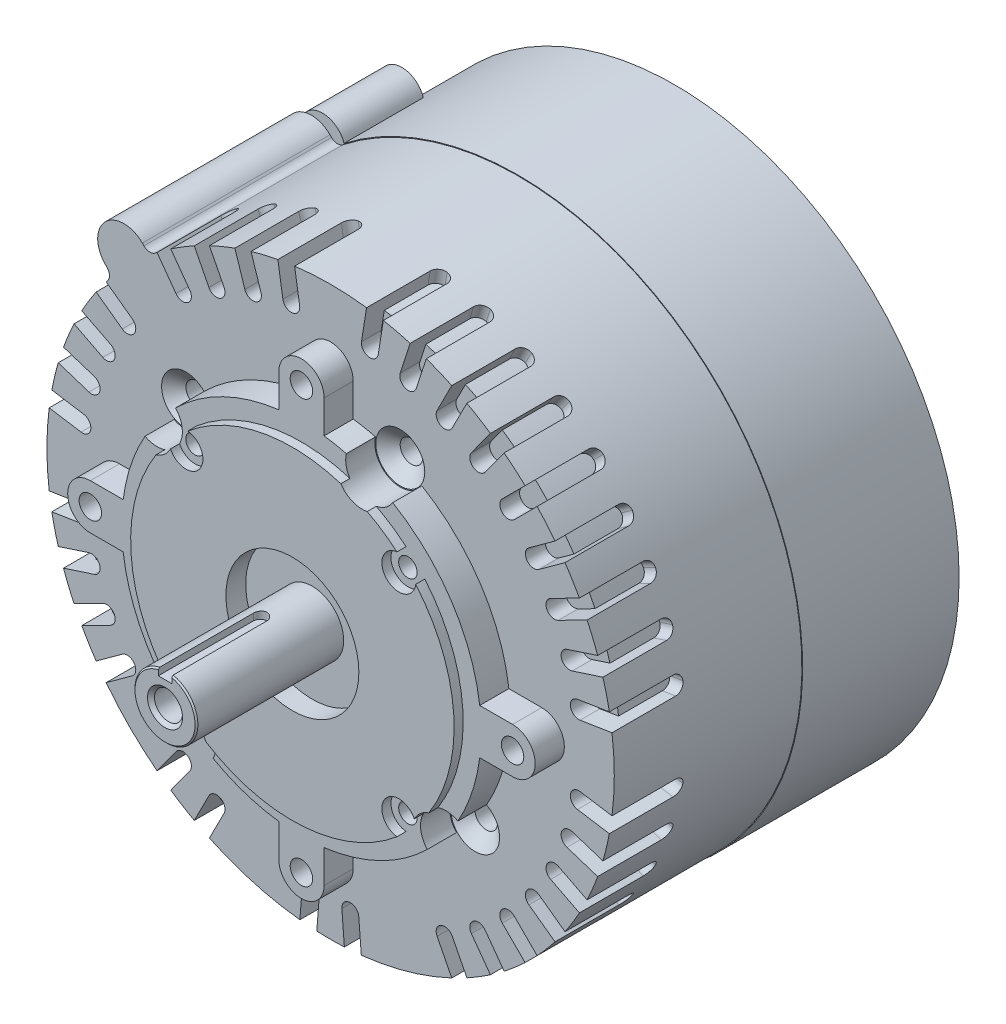
SolidWorks part; units mm, degrees
ref_plane "Front Plane" through (0, 0, 0) normal (0, 0, 1) x (1, 0, 0)
ref_plane "Top Plane" through (0, 0, 0) normal (0, 1, 0) x (1, 0, 0)
ref_plane "Right Plane" through (0, 0, 0) normal (1, 0, 0) x (0, 0, -1)
sketch "Sketch72" plane through (0, 0, 0) normal (0, 0, 1) x (1, 0, 0)
  circle A0 centre (0, 0) radius 100.5
  dimension "D1" = 201
extrude "Boss-Extrude34" add sketch "Sketch72" along normal blind 121.6 from offset 13.6 separate body
sketch "Sketch74" plane through (0, 0, 135.2) normal (0, 0, 1) x (1, 0, 0)
  circle A2 centre (0, 0) radius 100.25
  circle A3 centre (0, 0) radius 100.25
  dimension "D1" = 0.25
extrude "Cut-Extrude33" cut sketch "Sketch74" against normal blind 66.3 flip side to cut
sketch "Sketch73" plane through (0, 0, 0) normal (0, 0, 1) x (1, 0, 0)
  line L0 (-73.0441, 73.0441) -> (0, 0) construction
  line L1 (0, 0) -> (-43.4732, 0) construction
  line L2 (-66.5034, 79.5849) -> (-59.9627, 73.0441)
  line L3 (-59.9627, 73.0441) -> (-73.0441, 59.9627)
  line L4 (-73.0441, 59.9627) -> (-79.5849, 66.5034)
  circle A0 centre (-73.0441, 73.0441) radius 9.25
  point P9 (-73.0364, 73.0364)
  point P10 (-43.4732, 0)
  point P11 (0, 0)
  dimension "D1" = 18.5
  dimension "D2" = 45
  dimension "D3" = 103.3
extrude "Boss-Extrude35" add sketch "Sketch73" along normal up to surface (135.2 mm away) from surface contours A0 | A0 L4 L3 | A0 L3 L2 region at (-62.8846, 73.0441, 0) region at (-73.0441, 73.0441, 0) region at (-73.0441, 62.8846, 0) up to face at (100.25, 0, 135.2) starting at face at (100.25, 0, 68.9)
sketch "Sketch76" plane through (0, 0, 0) normal (0, 0, 1) x (1, 0, 0)
  line L0 (0, 52.4) -> (0, 74.6) construction
  line L1 (-8, 52.4) -> (-8, 74.6)
  line L2 (8, 52.4) -> (8, 74.6)
  line L3 (52.4, -8) -> (74.6, -8)
  line L4 (52.4, 8) -> (74.6, 8)
  line L5 (52.4, 0) -> (74.6, 0) construction
  line L6 (-8, -52.4) -> (-8, -74.6)
  line L7 (8, -52.4) -> (8, -74.6)
  line L8 (0, -52.4) -> (0, -74.6) construction
  line L9 (-52.4, 8) -> (-74.6, 8)
  line L10 (-52.4, -8) -> (-74.6, -8)
  line L11 (-52.4, 0) -> (-74.6, 0) construction
  line L12 (0, 0) -> (0, 52.4) construction
  line L13 (-51.0721, 39.189) -> (0, 0) construction
  line L14 (0, 0) -> (24.6352, 59.4747) construction
  line L15 (0, 0) -> (-39.189, -51.0721) construction
  circle A0 centre (0, 0) radius 63.5
  arc A1 (-8, 52.4) -> (8, 52.4) centre (0, 52.4) ccw
  arc A2 (8, 74.6) -> (-8, 74.6) centre (0, 74.6) ccw
  circle A3 centre (0, 0) radius 74.6 construction
  arc A4 (52.4, 8) -> (52.4, -8) centre (52.4, 0) ccw
  arc A5 (74.6, -8) -> (74.6, 8) centre (74.6, 0) ccw
  arc A6 (8, -52.4) -> (-8, -52.4) centre (0, -52.4) ccw
  arc A7 (-8, -74.6) -> (8, -74.6) centre (0, -74.6) ccw
  arc A8 (-52.4, -8) -> (-52.4, 8) centre (-52.4, 0) ccw
  arc A9 (-74.6, 8) -> (-74.6, -8) centre (-74.6, 0) ccw
  circle A10 centre (-51.0721, 39.189) radius 9
  circle A11 centre (0, 0) radius 64.375 construction
  circle A12 centre (-39.189, -51.0721) radius 9
  circle A13 centre (51.0721, -39.189) radius 9
  circle A14 centre (24.6352, 59.4747) radius 9
  point P5 (0, 63.5)
  point P15 (63.5, 0)
  point P22 (0, -63.5)
  point P29 (-63.5, 0)
  dimension "D1" = 127
  dimension "D2" = 149.2
  dimension "D3" = 8
  dimension "D5" = 128.75
  dimension "D6" = 18
  dimension "D7" = 52.5
  dimension "D8" = 22.5
  dimension "D9" = 142.5
  dimension "D4" = 4
extrude "Boss-Extrude36" add sketch "Sketch76" along normal blind 10.3 from surface contours L9 A9 L10 A0 | A8 L10 A0 L6 A6 L7 L3 A4 L4 L2 A1 L1 L9 | L2 A2 L1 A0 | L3 A5 L4 A0 | L6 A7 L7 A0 | L10 A8 L9 A0 | L1 A1 L2 A0 | L4 A4 L3 A0 | L7 A6 L6 A0 region at (0.1312, -0.0758, 0) region at (0, 54.6323, 0) region at (0, 72.1976, 0) region at (-72.1976, 0, 0) region at (-54.6323, 0, 0) region at (54.6323, 0, 0) region at (72.1976, 0, 0) region at (0, -72.1976, 0) region at (0, -54.6323, 0) starting at face at (-38.0816, 38.0816, 135.2)
sketch "Sketch78" plane through (0, 0, 0) normal (0, 0, 1) x (1, 0, 0)
  line L0 (-69.1197, 76.8979) -> (-76.8979, 69.1197) construction
  line L1 (-63.4628, 71.241) -> (-71.241, 63.4628)
  line L2 (-74.7765, 82.5547) -> (-82.5547, 74.7765)
  line L3 (-73.0441, 73.0441) -> (0, 0) construction
  arc A1 (-63.4628, 71.241) -> (-74.7765, 82.5547) centre (-69.1197, 76.8979) ccw
  arc A2 (-82.5547, 74.7765) -> (-71.241, 63.4628) centre (-76.8979, 69.1197) ccw
  circle A3 centre (0, 0) radius 103.25 construction
  point P2 (-73.0088, 73.0088)
  point P10 (0, 0)
  point P11 (-81.0955, 63.9068)
  point P13 (0, 0)
  dimension "D1" = 206.5
  dimension "D2" = 8
  dimension "D3" = 11
extrude "Boss-Extrude37" add sketch "Sketch78" against normal blind 28 from surface contours A1 L2 A2 L1 starting at face at (-73.614, 73.614, 68.9)
sketch "Sketch79" plane through (0, 0, 0) normal (0, 0, 1) x (1, 0, 0)
  line L0 (0, 0) -> (37.6181, 37.6181) construction
  line L1 (0, 0) -> (44.0536, 0) construction
  line L2 (0, 0) -> (37.6181, 37.6181) construction
  circle A0 centre (0, 0) radius 57.15
  circle A1 centre (0, 0) radius 53.2 construction
  circle A2 centre (37.6181, 37.6181) radius 6
  circle A3 centre (37.6181, -37.6181) radius 6
  circle A4 centre (-37.6181, -37.6181) radius 6
  circle A5 centre (-37.6181, 37.6181) radius 6
  point P6 (37.6181, -37.6181)
  dimension "D1" = 114.3
  dimension "D2" = 106.4
  dimension "D4" = 12
  dimension "D3" = 45
  dimension "D6" = 53.2
  dimension "D5" = 4
extrude "Boss-Extrude38" add sketch "Sketch79" along normal blind 3.2 from surface contours A5 A0 A4 A3 A2 region at (0, 0, 0) starting at face at (-1.0275, 0.6893, 145.5)
extrude "Cut-Extrude34" cut sketch "Sketch76<3>" along normal through all from surface contours A0 A10 | A0 A14 | A0 A13 | A0 A12 region at (-47.5743, 36.5051, 0) region at (22.9481, 55.4015, 0) region at (-36.5051, -47.5743, 0) region at (47.5743, -36.5051, 0) starting at face at (-38.0816, 38.0816, 135.2)
sketch "Sketch76<3>" plane through (0, 0, 0) normal (0, 0, 1) x (1, 0, 0) same geometry as "Sketch76"
sketch "Sketch80" plane through (0, 0, 0) normal (0, 0, 1) x (1, 0, 0)
  circle A0 centre (0, 0) radius 23.5
  dimension "D1" = 47
extrude "Cut-Extrude35" cut sketch "Sketch80" against normal blind 7 from surface starting at face at (0.9681, 4.0766, 148.7)
sketch "Sketch75" plane through (0, 0, 0) normal (0, 0, 1) x (1, 0, 0)
  circle A0 centre (0, 0) radius 11.115
  dimension "D1" = 22.23
extrude "Boss-Extrude39" add sketch "Sketch75" along normal offset from surface (52 mm away) 45 from surface contours A0 region at (0, 0, 0) up to face at (23.5, 0, 148.7) offset beyond the face yes starting at face at (23.5, 0, 141.7)
sketch "Sketch81" plane through (0, 0, 0) normal (0, 0, 1) x (1, 0, 0)
  line L1 (-2.39, 8.465) -> (2.39, 8.465)
  line L2 (-2.39, 8.465) -> (-2.39, 13.765)
  line L3 (-2.39, 13.765) -> (2.39, 13.765)
  line L4 (2.39, 8.465) -> (2.39, 13.765)
  line L5 (-2.39, 8.465) -> (2.39, 13.765) construction
  line L6 (-2.39, 13.765) -> (2.39, 8.465) construction
  circle A0 centre (0, 0) radius 11.115 construction
  circle A1 centre (0, 0) radius 11.115 construction
  point P0 (0, 11.115)
  point P9 (0, 0)
  dimension "D1" = 19.58
  dimension "D2" = 4.78
extrude "Cut-Extrude36" cut sketch "Sketch81" against normal blind 36 from surface starting at face at (11.115, 0, 193.7)
chamfer "Chamfer4" distance 0.5 angle 45 1 edges at (0, -11.115, 193.7)
sketch "Sketch82" plane through (0, 0, 0) normal (0, 0, 1) x (1, 0, 0)
  line L0 (-52.1953, 71.8407) -> (-65.6556, 90.3672) construction
  line L1 (-54.6224, 70.0774) -> (-68.0827, 88.6038)
  line L2 (-49.7683, 73.6041) -> (-63.2286, 92.1306)
  line L3 (0, 0) -> (-37.3757, 0) construction
  arc A0 (-77.1258, 64.0443) -> (-64.0443, 77.1258) centre (0, 0) ccw construction
  arc A1 (-54.6224, 70.0774) -> (-49.7683, 73.6041) centre (-52.1953, 71.8407) ccw
  arc A2 (-63.2286, 92.1306) -> (-68.0827, 88.6038) centre (-65.6556, 90.3672) ccw
  point P5 (-58.9255, 81.104)
  point P14 (-64.4395, 76.796)
  point P15 (-59.0191, 81.2329)
  point P16 (0, 0)
  dimension "D1" = 54
  dimension "D2" = 6
  dimension "D3" = 22.9
extrude "Cut-Extrude37" cut sketch "Sketch82" against normal blind 25.482 from surface starting at face at (-38.0816, 38.0816, 135.2)
fillet "Fillet6" radius 3 3 edges at (-57.9743, 74.6908, 109.718) (-50.432, 69.4137, 109.718) (-53.1202, 78.2175, 109.718)
pattern_circular "CirPattern1" count 40 every 9 about axis through (0, 0, 135.2) along (0, 0, 1) skipping 1, 6, 11, 12, 13, 14, 15, 16, 17, 18, 26, 36 of "Fillet6", "Cut-Extrude37"
fillet "Fillet7" 2 edges at (-2.39, 9.66, 157.7) (2.39, 9.66, 157.7) type full round first side face at (-2.39, 9.8477, 179.15) second side face at (2.39, 9.7452, 179.25) middle face at (0, 9.725, 157.7)
sketch "Sketch84" plane through (0, 0, 0) normal (0, 0, 1) x (1, 0, 0)
  line L0 (8.7639, -111.3557) -> (6.9672, -88.5263) construction
  line L3 (5.7731, -111.591) -> (3.9764, -88.7616)
  line L4 (11.7546, -111.1203) -> (9.9579, -88.2909)
  line L5 (0, 0) -> (0, -77.8847) construction
  line L6 (-8.7639, -111.3557) -> (-6.9672, -88.5263) construction
  line L7 (-5.7731, -111.591) -> (-3.9764, -88.7616)
  line L8 (-11.7546, -111.1203) -> (-9.9579, -88.2909)
  line L9 (-50.7107, -99.5254) -> (-40.3144, -79.1214) construction
  line L10 (-53.3838, -98.1635) -> (-42.9874, -77.7594)
  line L11 (-48.0377, -100.8874) -> (-37.6413, -80.4834)
  line L12 (-65.6556, -90.3672) -> (-52.1953, -71.8407) construction
  line L13 (-63.2286, -92.1306) -> (-49.7683, -73.6041)
  line L14 (-68.0827, -88.6038) -> (-54.6224, -70.0774)
  line L15 (0, 0) -> (-8.7639, -111.3557) construction
  line L16 (0, 0) -> (-65.6556, -90.3672) construction
  arc A2 (5.7731, -111.591) -> (11.7546, -111.1203) centre (8.7639, -111.3557) ccw
  arc A3 (9.9579, -88.2909) -> (3.9764, -88.7616) centre (6.9672, -88.5263) ccw
  arc A4 (-79.3043, -61.3261) -> (42.8191, -90.6454) centre (0, 0) ccw construction
  arc A6 (-5.7731, -111.591) -> (-11.7546, -111.1203) centre (-8.7639, -111.3557) cw
  arc A7 (-9.9579, -88.2909) -> (-3.9764, -88.7616) centre (-6.9672, -88.5263) cw
  arc A8 (-53.3838, -98.1635) -> (-48.0377, -100.8874) centre (-50.7107, -99.5254) ccw
  arc A9 (-37.6413, -80.4834) -> (-42.9874, -77.7594) centre (-40.3144, -79.1214) ccw
  arc A10 (-63.2286, -92.1306) -> (-68.0827, -88.6038) centre (-65.6556, -90.3672) cw
  arc A11 (-54.6224, -70.0774) -> (-49.7683, -73.6041) centre (-52.1953, -71.8407) cw
  point P2 (7.8655, -99.941)
  point P13 (0, 0)
  point P15 (-7.8655, -99.941)
  point P20 (0, 0)
  point P25 (-45.5125, -89.3234)
  point P32 (-58.9255, -81.104)
  point P40 (0, 0)
  dimension "D1" = 6
  dimension "D2" = 4.5
  dimension "D3" = 22.9
  dimension "D5" = 31.5
  dimension "D4" = 2
extrude "Cut-Extrude38" cut sketch "Sketch84" against normal blind 25.482 from surface starting at face at (-1.0275, 0.6893, 135.2)
fillet "Fillet8" radius 3 12 edges at (10.4053, -93.9759, 109.718) (6.7318, -85.5355, 109.718) (-4.4238, -94.4466, 109.718) (-6.7318, -85.5355, 109.718) (-40.2302, -85.5644, 109.718) (-38.9524, -76.4484, 109.718) (-53.1202, -78.2175, 109.718) (-50.432, -69.4137, 109.718) (4.4238, -94.4466, 109.718) (-10.4053, -93.9759, 109.718) (-45.5763, -82.8404, 109.718) (-57.9743, -74.6908, 109.718)
sketch "Sketch83" plane through (0, 0, 0) normal (0, 0, 1) x (1, 0, 0)
  circle A0 centre (0, 0) radius 95.5
  dimension "D1" = 191
extrude "Boss-Extrude40" add sketch "Sketch83" along normal offset from surface (59.3 mm away) 7 from surface up to face at (-1.0275, 0.6893, 135.2) starting at face at (-46.3547, 46.3547, 68.9)
sketch "Sketch85" plane through (0, 0, 145.5) normal (0, 0, 1) x (1, 0, 0)
  point P0 (-37.6181, 37.6181)
  point P3 (37.6181, 37.6181)
  point P6 (37.6181, -37.6181)
  point P9 (-37.6181, -37.6181)
hole_wizard "5/16-18 Tapped Hole1" positions "Sketch85" profile "Sketch86" tap size "5/16-18" standard "ANSI Inch"
sketch "Sketch86" plane through (-37.6181, 37.6181, 145.5) normal (1, 0, 0) x (0, -1, 0)
  line L0 (0, 0) -> (0, 16.9611)
  line L1 (0, 16.9611) -> (3.2639, 15)
  line L2 (3.2639, 15) -> (3.2639, 0)
  line L5 (3.2639, 0) -> (0, 0)
  line L10 (0, 16.9611) -> (-3.2639, 15) construction
  line L11 (0, -6.35) -> (0, 107.95) construction
  dimension "Tap Drill Dia." = 6.5278
  dimension "Tap Drill Depth" = 15
  dimension "Drill Angle" = 118
cosmetic thread "Hole Thread1" parameters "D1"=15.88, "D2"=7.9375
cosmetic thread "Hole Thread2" parameters "D1"=15.88, "D2"=7.9375
cosmetic thread "Hole Thread3" parameters "D1"=15.88, "D2"=7.9375
cosmetic thread "Hole Thread4" parameters "D1"=15.88, "D2"=7.9375
sketch "Sketch87" plane through (0, 0, 145.5) normal (0, 0, 1) x (1, 0, 0)
  point P0 (-74.6, 0)
  point P3 (0, 74.6)
  point P6 (74.6, 0)
  point P9 (0, -74.6)
hole_wizard "3/8-16 Tapped Hole2" positions "Sketch87" profile "Sketch88" tap size "3/8-16" standard "ANSI Inch"
sketch "Sketch88" plane through (-74.6, 0, 145.5) normal (1, 0, 0) x (0, -1, 0)
  line L0 (0, 0) -> (0, 20.3847)
  line L1 (0, 20.3847) -> (3.9687, 18)
  line L2 (3.9687, 18) -> (3.9687, 0)
  line L5 (3.9687, 0) -> (0, 0)
  line L10 (0, 20.3847) -> (-3.9688, 18) construction
  line L11 (0, -6.35) -> (0, 107.95) construction
  dimension "Tap Drill Dia." = 7.9375
  dimension "Tap Drill Depth" = 18
  dimension "Drill Angle" = 118
cosmetic thread "Hole Thread5" parameters "D1"=19.05, "D2"=9.525
cosmetic thread "Hole Thread6" parameters "D1"=19.05, "D2"=9.525
cosmetic thread "Hole Thread7" parameters "D1"=19.05, "D2"=9.525
cosmetic thread "Hole Thread8" parameters "D1"=19.05, "D2"=9.525
hole_wizard "5/16 (0.3125) Diameter Hole3" positions "3DSketch6" profile "Sketch89" hole size "5/16" standard "ANSI Inch"
sketch3d "3DSketch6"
  line L0 (-39.189, -51.0721, 145.5) -> (-39.189, -51.0721, 135.2) construction
  line L1 (51.0721, -39.189, 145.5) -> (51.0721, -39.189, 135.2) construction
  line L2 (24.6352, 59.4747, 145.5) -> (24.6352, 59.4747, 135.2) construction
  line L3 (-51.0721, 39.189, 145.5) -> (-51.0721, 39.189, 135.2) construction
  point P0 (-39.189, -51.0721, 135.2)
  point P4 (51.0721, -39.189, 135.2)
  point P8 (24.6352, 59.4747, 135.2)
  point P12 (-51.0721, 39.189, 135.2)
sketch "Sketch89" plane through (-39.189, -51.0721, 135.2) normal (1, 0, 0) x (0, -1, 0)
  line L0 (0, 0) -> (0, 25.3147)
  line L1 (0, 25.3147) -> (3.9687, 22.93)
  line L2 (3.9687, 22.93) -> (3.9687, 3.928)
  line L3 (3.9687, 3.928) -> (8.65, 0)
  line L5 (8.65, 0) -> (0, 0)
  line L6 (-3.9687, 3.928) -> (-8.65, 0) construction
  line L10 (0, 25.3147) -> (-3.9688, 22.93) construction
  line L11 (0, -6.35) -> (0, 107.95) construction
  dimension "Hole Dia." = 7.9375
  dimension "Hole Depth" = 22.93
  dimension "Near C'Sink Dia." = 17.3
  dimension "Near C'Sink Angle" = 100
  dimension "Drill Angle" = 118
sketch "Sketch90" plane through (0, 0, 193.7) normal (0, 0, 1) x (1, 0, 0)
  point P0 (0, 0)
hole_wizard "7/16-20 Tapped Hole1" positions "Sketch90" profile "Sketch92" tap size "7/16-20" standard "ANSI Inch"
sketch "Sketch92" plane through (0, 0, 193.7) normal (1, 0, 0) x (0, -1, 0)
  line L0 (0, 0) -> (0, 37.9806)
  line L1 (0, 37.9806) -> (4.9606, 35)
  line L2 (4.9606, 35) -> (4.9606, 1.2306)
  line L3 (4.9606, 1.2306) -> (6.1913, 0)
  line L5 (6.1913, 0) -> (0, 0)
  line L6 (-4.9606, 1.2306) -> (-6.1913, 0) construction
  line L10 (0, 37.9806) -> (-4.9606, 35) construction
  line L11 (0, -6.35) -> (0, 107.95) construction
  dimension "Tap Drill Dia." = 9.9212
  dimension "Tap Drill Depth" = 35
  dimension "Near C'Sink Dia." = 12.3825
  dimension "Near C'Sink Angle" = 90
  dimension "Drill Angle" = 118
cosmetic thread "Hole Thread13" parameters "D1"=30, "D2"=11.1125
fillet "Fillet9" radius 3 2 edges at (-64.0443, 77.1258, 102.05) (-77.1258, 64.0443, 102.05)
